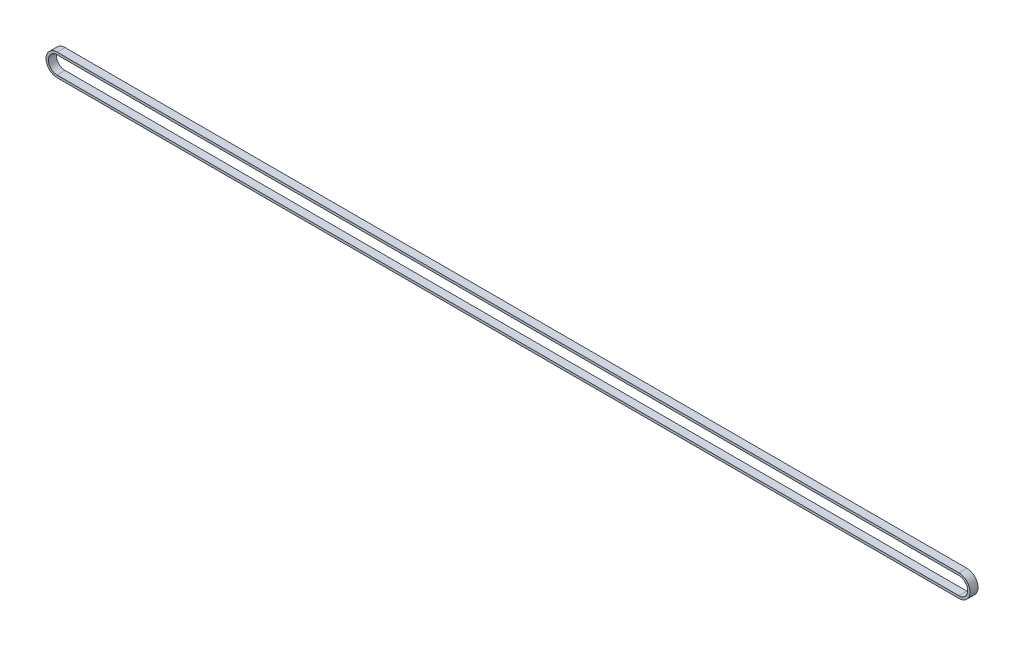
SolidWorks part; units mm, degrees
material "Caoutchouc silicone"
ref_plane "Plan de face" through (0, 0, 0) normal (0, 0, 1) x (1, 0, 0)
ref_plane "Plan de dessus" through (0, 0, 0) normal (0, 1, 0) x (1, 0, 0)
ref_plane "Plan de droite" through (0, 0, 0) normal (1, 0, 0) x (0, 0, -1)
sketch "Esquisse1" plane through (0, 0, 0) normal (0, 0, 1) x (1, 0, 0)
  line L0 (-284, 0) -> (284, 0) construction
  line L3 (-284, 5.5) -> (284, 5.5)
  line L6 (-284, -5.5) -> (284, -5.5)
  line L7 (284, 0) -> (-284, 0) construction
  line L8 (284, -7) -> (-284, -7)
  line L9 (284, 7) -> (-284, 7)
  arc A4 (-284, 5.5) -> (-284, -5.5) centre (-284, 0) ccw
  arc A5 (284, -5.5) -> (284, 5.5) centre (284, 0) ccw
  arc A6 (284, -7) -> (284, 7) centre (284, 0) ccw
  arc A7 (-284, 7) -> (-284, -7) centre (-284, 0) ccw
  point P3 (0, 0)
  point P8 (0, 0)
  point P15 (0, 0)
  point P16 (0, 0)
  point P18 (14.6563, 30.9585)
  dimension "D1" = 5.5
  dimension "D2" = 7
  dimension "D3" = 568
extrude "Boss.-Extru.1" add sketch "Esquisse1" along normal blind 2.5 and the other way blind 2.5
